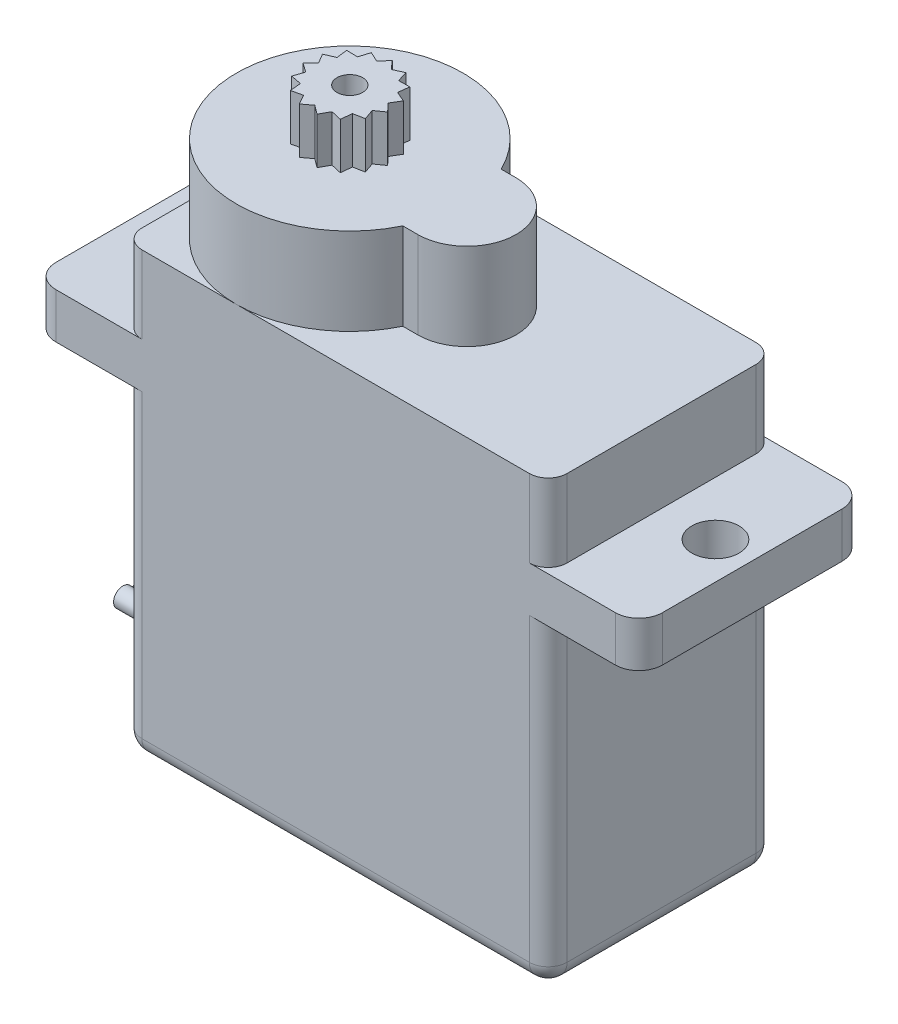
SolidWorks part; units mm, degrees
material "Plain Carbon Steel"
ref_plane "Front Plane" through (0, 0, 0) normal (0, 0, 1) x (1, 0, 0)
ref_plane "Top Plane" through (0, 0, 0) normal (0, 1, 0) x (1, 0, 0)
ref_plane "Right Plane" through (0, 0, 0) normal (1, 0, 0) x (0, 0, -1)
sketch "Sketch1" plane through (0, 0, 0) normal (0, 0, 1) x (1, 0, 0)
  line L0 (0, 0) -> (0, 16.9)
  line L1 (0, 23.4) -> (22.5, 23.4)
  line L2 (22.5, 16.9) -> (22.5, 0)
  line L3 (22.5, 0) -> (0, 0)
  line L5 (22.5, 16.9) -> (27.3, 16.9)
  line L6 (27.3, 16.9) -> (27.3, 19.3)
  line L7 (27.3, 19.3) -> (22.5, 19.3)
  line L8 (-4.8, 19.3) -> (-4.8, 16.9)
  line L9 (-4.8, 16.9) -> (0, 16.9)
  line L11 (22.5, 23.4) -> (22.5, 19.3)
  line L12 (0, 19.3) -> (0, 23.4)
  line L19 (0, 19.3) -> (-4.8, 19.3)
  dimension "D1" = 16.9
  dimension "D2" = 22.5
  dimension "D3" = 6.5
  dimension "D4" = 32.1
  dimension "D5" = 2.4
extrude "Boss-Extrude1" add sketch "Sketch1" along normal mid plane 12
sketch "Sketch5" plane through (0, 23.4, 0) normal (0, 1, 0) x (1, 0, 0)
  line L0 (0, -6) -> (0, 6) construction
  line L1 (22.5, 6) -> (0, 6) construction
  line L2 (6, 0) -> (11.25, 0) construction
  line L6 (12.2, 2.6) -> (11.4074, 2.6)
  line L7 (12.2, -2.6) -> (11.4074, -2.6)
  arc A0 (11.4074, 2.6) -> (11.4074, -2.6) centre (6, 0) ccw
  arc A1 (12.2, 2.6) -> (12.2, -2.6) centre (12.2, 0) cw
  point P1 (0, 0)
  point P6 (11.25, 6)
  point P18 (14.8, 0)
  dimension "D1" = 12
  dimension "D2" = 0
  dimension "D3" = 5.25
  dimension "D4" = 5.2
  dimension "D5" = 14.8
extrude "Boss-Extrude3" add sketch "Sketch5" along normal blind 4.6
sketch "Sketch6" plane through (0, 28, 0) normal (0, 1, 0) x (1, 0, 0)
  line L0 (5.6154, 1.8096) -> (6, 2.25)
  line L1 (6, 0) -> (5.6154, 1.8096) construction
  line L2 (6, 0) -> (6.3846, 1.8096) construction
  line L3 (6.3846, 1.8096) -> (5.6154, 1.8096) construction
  line L4 (6, 2.25) -> (6.3846, 1.8096)
  line L5 (6.3846, 1.8096) -> (6.9152, 2.0555)
  line L6 (6.9152, 2.0555) -> (7.0874, 1.4967)
  line L7 (7.0874, 1.4967) -> (7.6721, 1.5055)
  line L8 (7.6721, 1.5055) -> (7.6021, 0.925)
  line L9 (7.6021, 0.925) -> (8.1399, 0.6953)
  line L10 (8.1399, 0.6953) -> (7.8399, 0.1934)
  line L11 (7.8399, 0.1934) -> (8.2377, -0.2352)
  line L12 (8.2377, -0.2352) -> (7.7595, -0.5717)
  line L13 (7.7595, -0.5717) -> (7.9486, -1.125)
  line L14 (7.9486, -1.125) -> (7.3748, -1.2379)
  line L15 (7.3748, -1.2379) -> (7.3225, -1.8203)
  line L16 (7.3225, -1.8203) -> (6.7525, -1.6901)
  line L17 (6.7525, -1.6901) -> (6.4678, -2.2008)
  line L18 (6.4678, -2.2008) -> (6, -1.85)
  line L19 (6, -1.85) -> (5.5322, -2.2008)
  line L20 (5.5322, -2.2008) -> (5.2475, -1.6901)
  line L21 (5.2475, -1.6901) -> (4.6775, -1.8203)
  line L22 (4.6775, -1.8203) -> (4.6252, -1.2379)
  line L23 (4.6252, -1.2379) -> (4.0514, -1.125)
  line L24 (4.0514, -1.125) -> (4.2405, -0.5717)
  line L25 (4.2405, -0.5717) -> (3.7623, -0.2352)
  line L26 (3.7623, -0.2352) -> (4.1601, 0.1934)
  line L27 (4.1601, 0.1934) -> (3.8601, 0.6953)
  line L28 (3.8601, 0.6953) -> (4.3979, 0.925)
  line L29 (4.3979, 0.925) -> (4.3279, 1.5055)
  line L30 (4.3279, 1.5055) -> (4.9126, 1.4967)
  line L31 (4.9126, 1.4967) -> (5.0848, 2.0555)
  line L32 (5.0848, 2.0555) -> (5.6154, 1.8096)
  circle A0 centre (6, 0) radius 2.25 construction
  circle A1 centre (6, 0) radius 0.68
  circle A2 centre (6, 0) radius 1.85 construction
  point P6 (6, 1.8096)
  point P53 (6, 0)
  dimension "D1" = 4.5
  dimension "D2" = 1.36
  dimension "D3" = 3.7
  dimension "D4" = 24
  dimension "D5" = 15
extrude "Boss-Extrude4" add sketch "Sketch6" along normal blind 2.45
sketch "Sketch2" plane through (0, 19.3, 0) normal (0, 1, 0) x (1, 0, 0)
  line L0 (-4.8, 0) -> (-2.85, 0) construction
  line L1 (-4.8, -6) -> (-4.8, 6) construction
  line L2 (25.35, 0) -> (27.3, 0) construction
  line L3 (27.3, -6) -> (27.3, 6) construction
  line L4 (-2.85, 1.25) -> (-2.85, 6)
  line L5 (0, 6) -> (-4.8, 6) construction
  line L6 (-1.6, 0) -> (0, 0)
  line L7 (0, -6) -> (0, 6) construction
  circle A0 centre (-2.85, 0) radius 1.25
  circle A1 centre (25.35, 0) radius 1.25
  dimension "D2" = 1.6
  dimension "D1" = 2.5
extrude "Cut-Extrude6" cut sketch "Sketch2" against normal blind 10 contours A1 | A0 region at (25.35, 19.3, 0)
fillet "Fillet1" radius 1 12 edges at (0, 0, 0) (11.25, 0, 6) (22.5, 0, 0) (11.25, 0, -6) (0, 8.45, -6) (0, 21.35, -6) (0, 8.45, 6) (0, 21.35, 6) (22.5, 21.35, 6) (22.5, 21.35, -6) (22.5, 8.45, -6) (22.5, 8.45, 6)
fillet "Fillet2" radius 1.25 4 edges at (27.3, 18.1, -6) (-4.8, 18.1, -6) (-4.8, 18.1, 6) (27.3, 18.1, 6)
sketch "Sketch7" plane through (0, 0, 0) normal (-1, 0, 0) x (0, 0, 1)
  line L0 (-0.5437, 2.2043) -> (-0.4563, 2.2043)
  line L1 (0.4563, 2.2043) -> (0.5437, 2.2043)
  line L2 (0.5437, 1.7957) -> (0.4563, 1.7957)
  line L3 (-0.4563, 1.7957) -> (-0.5437, 1.7957)
  arc A0 (0.4563, 2.2043) -> (-0.4563, 2.2043) centre (0, 2) ccw
  arc A1 (0.5437, 1.7957) -> (0.5437, 2.2043) centre (1, 2) ccw
  arc A2 (-0.5437, 2.2043) -> (-0.5437, 1.7957) centre (-1, 2) ccw
  arc A3 (-0.4563, 1.7957) -> (0.4563, 1.7957) centre (0, 2) ccw
  dimension "D1" = 1
  dimension "D2" = 2
extrude "Boss-Extrude5" add sketch "Sketch7" along normal blind 5
ref_axis "Axis1" through (6, 30.45, 0) along (0, -1, 0)
